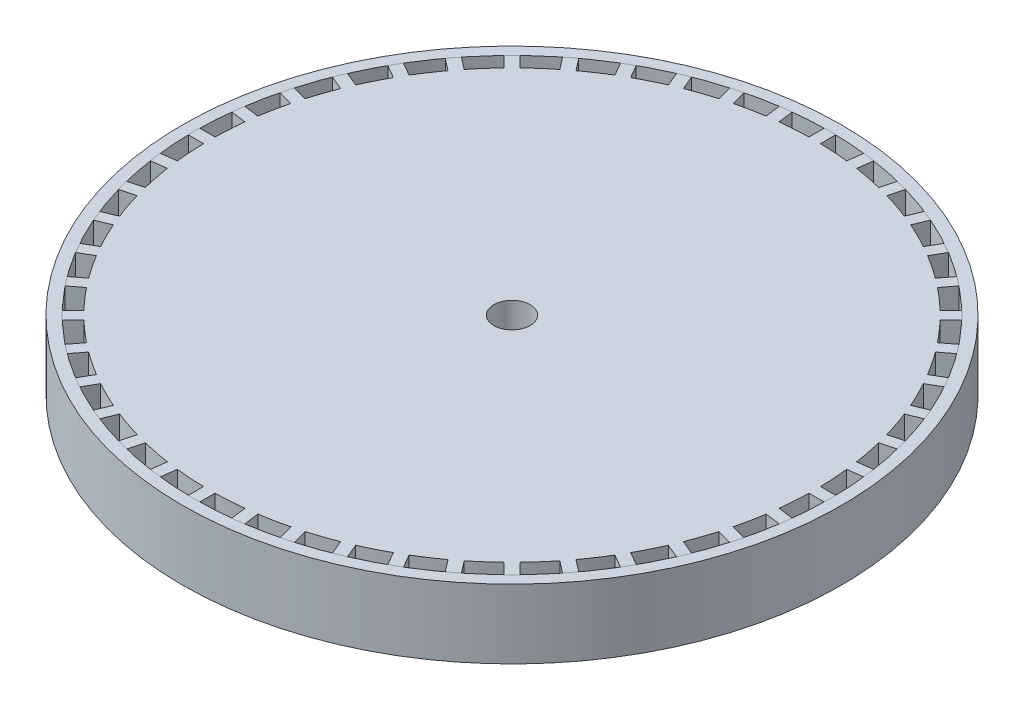
SolidWorks part; units mm, degrees
material "Nickel"
ref_plane "Front Plane" through (0, 0, 0) normal (0, 0, 1) x (1, 0, 0)
ref_plane "Top Plane" through (0, 0, 0) normal (0, 1, 0) x (1, 0, 0)
ref_plane "Right Plane" through (0, 0, 0) normal (1, 0, 0) x (0, 0, -1)
sketch "Sketch1" plane through (0, 0, 0) normal (0, 1, 0) x (1, 0, 0)
  circle A0 centre (0, 0) radius 83.4644
  circle A1 centre (0, 0) radius 5
  circle A2 centre (0, 0) radius 87.6808
  circle A3 centre (0, 0) radius 90.8558
  point P135 (0, 0)
  dimension "D1" = 166.9288
  dimension "D2" = 10
  dimension "D4" = 175.3616
  dimension "D3" = 3.175
extrude "Boss-Extrude1" add sketch "Sketch1" along normal mid plane 19.05 contours A0 A1 | A3 A2 region at (-81.1037, 0, 0) region at (-88.286, 0, 0)
sketch "Sketch2" plane through (0, 0, 0) normal (0, 1, 0) x (1, 0, 0)
  line L0 (83.4493, 1.5875) -> (87.6808, 1.5875)
  line L1 (87.6808, 1.5875) -> (87.6808, -1.5875)
  line L2 (87.6808, -1.5875) -> (83.4493, -1.5875)
  line L3 (83.4493, -1.5875) -> (83.4493, 1.5875)
  line L4 (0, 0) -> (87.6808, 0) construction
  circle A1 centre (0, 0) radius 83.4644 construction
  dimension "D1" = 87.6808
  dimension "D2" = 3.175
extrude "Boss-Extrude2" add sketch "Sketch2" along direction (0, 1, 0) on the side of the normal up to surface (9.525 mm away) and the other way up to surface (9.525 mm away) up to face at (0, 9.525, 5) other way up to face at (0, -9.525, 5)
ref_axis "Axis1" through (0, 6.6675, 0) along (0, -1, 0)
pattern_circular "CirPattern1" count 48 over 360 about axis through (0, 6.6675, 0) along (0, -1, 0) of "Boss-Extrude2"
sketch "Sketch3" plane through (0, 0, 0) normal (0, 1, 0) x (1, 0, 0)
  line L0 (0, 0) -> (57.15, 0) construction
  ellipse E0 centre (44.45, 0) end of major axis (31.75, 0) minor radius 4.7625
  dimension "D1" = 31.75
  dimension "2.75" = 57.15
  dimension "3/8" = 9.525
sketch "Sketch4" plane through (0, 0, 0) normal (0, 1, 0) x (1, 0, 0)
  circle A0 centre (0, 0) radius 5
  circle A1 centre (0, 0) radius 31.75
  dimension "D1" = 63.5
  dimension "D2" = 10
extrude "Boss-Extrude3" [suppressed] add sketch "Sketch4" along normal mid plane 19.05
equation "\"D1@Sketch1\"=2*\"rotor base@[TP] [Turb] Turbine.Assembly\""
equation "\"D1@Sketch2\"=\"rotor tip@[TP] [Turb] Turbine.Assembly\""
equation "\"D4@Sketch1\"=2*\"rotor tip@[TP] [Turb] Turbine.Assembly\""
equation "\"D3@Sketch1\"=\"shroud thickness@[TP] [Turb] Turbine.Assembly\""
